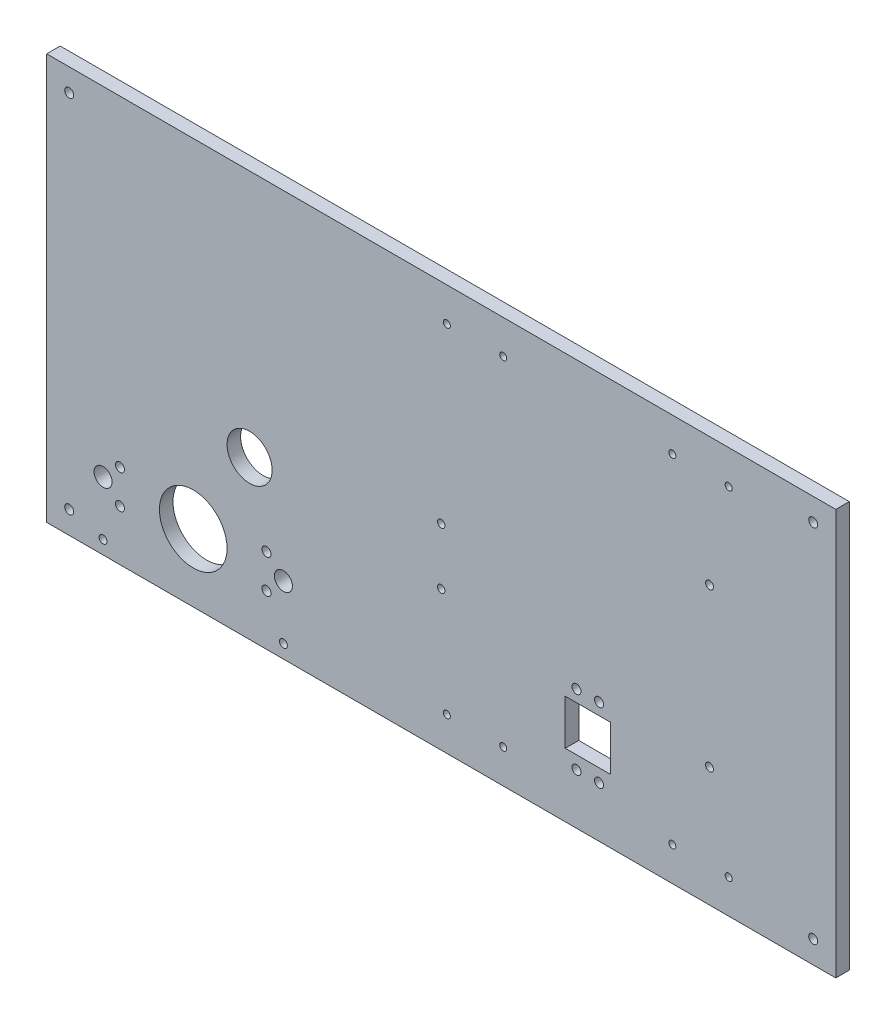
SolidWorks part; units mm, degrees
material "Faia"
ref_plane "Plano frontal" through (0, 0, 0) normal (0, 0, 1) x (1, 0, 0)
ref_plane "Plano superior" through (0, 0, 0) normal (0, 1, 0) x (1, 0, 0)
ref_plane "Plano direito" through (0, 0, 0) normal (1, 0, 0) x (0, 0, -1)
sketch "Esboço1" plane through (0, 0, 0) normal (0, 0, 1) x (1, 0, 0)
  line L0 (175, 0) -> (-175, 0) construction
  line L1 (-175, 90) -> (175, 90)
  line L2 (-175, 90) -> (-175, -90)
  line L3 (-175, -90) -> (175, -90)
  line L4 (175, 90) -> (175, -90)
  line L5 (-175, 90) -> (175, -90) construction
  line L6 (-175, -90) -> (175, 90) construction
  line L8 (-118.2276, -60) -> (-99.3617, -60) construction
  line L9 (25, 5) -> (25, -80) construction
  line L10 (105, 5) -> (25, 5) construction
  line L11 (25, -80) -> (105, -80) construction
  line L12 (-110, -54.1086) -> (-110, -81.356) construction
  line L13 (55, -41.75) -> (75, -41.75)
  line L14 (55, -41.75) -> (55, -61.75)
  line L15 (55, -61.75) -> (75, -61.75)
  line L16 (75, -41.75) -> (75, -61.75)
  line L17 (55, -41.75) -> (75, -61.75) construction
  line L18 (55, -61.75) -> (75, -41.75) construction
  line L26 (95, 0) -> (-255, 0) construction
  circle A0 centre (105, 5) radius 1.5 construction
  circle A1 centre (105, -80) radius 1.5 construction
  circle A2 centre (25, -80) radius 1.5 construction
  circle A3 centre (25, 5) radius 1.5 construction
  circle A4 centre (-142.5, -52.5) radius 2
  circle A5 centre (-77.5, -52.5) radius 2
  circle A6 centre (-110, -60) radius 15
  circle A7 centre (-70, -60) radius 4
  circle A8 centre (-150, -60) radius 4
  circle A9 centre (-77.5, -67.5) radius 2
  circle A10 centre (-142.5, -67.5) radius 2
  circle A11 centre (0, -3) radius 1.65
  circle A12 centre (0, -28) radius 1.65
  point P0 (0, 0)
  point P21 (5, 0)
  point P23 (65, -51.75)
  point P28 (65, -80)
  dimension "D5" = 3
  dimension "D8" = 32.5
  dimension "D16" = 30
  dimension "D19" = 8
  dimension "D20" = 80
  dimension "D10" = 4
  dimension "D21" = 3.3
  dimension "D1" = 350
  dimension "D2" = 180
  dimension "D3" = 70
  dimension "D4" = 85
  dimension "D7" = 80
  dimension "D9" = 15
  dimension "D11" = 25
  dimension "D12" = 10
  dimension "D13" = 20
  dimension "D14" = 20
  dimension "D15" = 28.25
  dimension "D17" = 65
  dimension "D18" = 30
  dimension "D22" = 25
  dimension "D23" = 8
  dimension "D6" = 2
extrude "Ressalto-extrusão1" add sketch "Esboço1" along normal blind 6 contours L4 L1 L2 L3 A3 A1 A0 A2 region at (1.1072, 1.1733, 0)
sketch "Esboço2" plane through (0, 0, 6) normal (0, 0, 1) x (1, 0, 0)
  line L0 (175, 0) -> (-175, 0) construction
  line L1 (-175, 90) -> (175, 90)
  line L2 (-175, 90) -> (-175, -90)
  line L3 (-175, -90) -> (175, -90)
  line L4 (175, 90) -> (175, -90)
  line L5 (-175, 90) -> (175, -90) construction
  line L6 (-175, -90) -> (175, 90) construction
  line L7 (165, 80) -> (165, 90) construction
  line L8 (165, -80) -> (165, -90) construction
  line L9 (-175, 90) -> (175, 90) construction
  circle A0 centre (165, -80) radius 2
  circle A1 centre (165, 80) radius 2
  circle A2 centre (-165, 80) radius 2
  circle A3 centre (-165, -80) radius 2
  point P0 (0, 0)
  point P16 (0.5357, 0)
  dimension "D3" = 4
  dimension "D2" = 180
  dimension "D4" = 10
  dimension "D5" = 10
  dimension "D6" = 10
  dimension "D7" = 10
extrude "espacador" cut sketch "Esboço2" against normal blind 10 contours A2 | A1 | A0 | A3 region at (165, -80, 6) region at (165, 80, 6) region at (-165, 80, 6) region at (-165, -80, 6)
sketch "Esboço3" plane through (0, 0, 6) normal (0, 0, 1) x (1, 0, 0)
  line L1 (-175, -90) -> (175, -90) construction
  line L2 (60, -67.5) -> (70, -67.5) construction
  line L3 (55, -61.75) -> (75, -61.75) construction
  circle A0 centre (70, -67.5) radius 2
  circle A1 centre (70, -36.5) radius 2
  circle A2 centre (60, -36.5) radius 2
  circle A3 centre (60, -67.5) radius 2
  point P2 (65, -67.5)
  point P13 (65, -61.75)
  dimension "D2" = 4
  dimension "D3" = 22.5
  dimension "D4" = 31
  dimension "D5" = 10
extrude "Corte-extrusão2" cut sketch "Esboço3" against normal blind 10
sketch "Esboço4" plane through (0, 0, 6) normal (0, 0, 1) x (1, 0, 0)
  line L0 (102.5, 75) -> (127.5, 75) construction
  line L1 (2.5, 75) -> (27.5, 75) construction
  line L2 (65, -41.75) -> (65, 53.8452) construction
  line L3 (55, -41.75) -> (75, -41.75) construction
  line L4 (127.5, -75) -> (102.5, -75) construction
  line L5 (2.5, -75) -> (27.5, -75) construction
  line L6 (175, 0) -> (131.6351, 0) construction
  line L7 (175, 90) -> (175, -90) construction
  circle A0 centre (102.5, 75) radius 1.55
  circle A1 centre (127.5, 75) radius 1.55
  circle A2 centre (2.5, 75) radius 1.55
  circle A3 centre (27.5, 75) radius 1.55
  circle A4 centre (127.5, -75) radius 1.55
  circle A5 centre (102.5, -75) radius 1.55
  circle A6 centre (2.5, -75) radius 1.55
  circle A7 centre (27.5, -75) radius 1.55
  point P8 (15, 75)
  point P9 (115, 75)
  point P22 (15, -75)
  point P23 (115, -75)
  dimension "D2" = 3.1
  dimension "D4" = 3.1
  dimension "D1" = 25
  dimension "D3" = 150
  dimension "D5" = 100
extrude "Corte-extrusão3" cut sketch "Esboço4" against normal blind 10
sketch "Esboço5" plane through (0, 0, 6) normal (0, 0, 1) x (1, 0, 0)
  line L0 (-175, -90) -> (175, -90) construction
  line L1 (-175, 90) -> (-175, -90) construction
  circle A0 centre (-85, -20) radius 10
  dimension "D1" = 20
  dimension "D2" = 70
  dimension "D3" = 90
extrude "fios" cut sketch "Esboço5" against normal blind 10
sketch "Esboço6" plane through (0, 0, 6) normal (0, 0, 1) x (1, 0, 0)
  line L0 (119, -37) -> (119, 33) construction
  line L1 (175, 90) -> (175, -90) construction
  line L2 (-175, 90) -> (175, 90) construction
  circle A0 centre (119, -37) radius 1.75
  circle A1 centre (119, 33) radius 1.75
  dimension "D2" = 3.5
  dimension "D1" = 70
  dimension "D3" = 56
  dimension "D4" = 57
extrude "Corte-extrusão5" cut sketch "Esboço6" against normal blind 10
sketch "Esboço7" plane through (0, 0, 6) normal (0, 0, 1) x (1, 0, 0)
  line L0 (-150, -84) -> (-70, -84) construction
  line L1 (-175, -90) -> (175, -90) construction
  circle A0 centre (-70, -84) radius 1.75
  circle A1 centre (-150, -84) radius 1.75
  circle A3 centre (-150, -60) radius 4 construction
  point P4 (0, 0)
  point P5 (0, 0)
  dimension "D1" = 80
  dimension "D2" = 0
  dimension "D4" = 3.5
  dimension "D3" = 6
extrude "Corte-extrusão6" cut sketch "Esboço7" against normal blind 10
